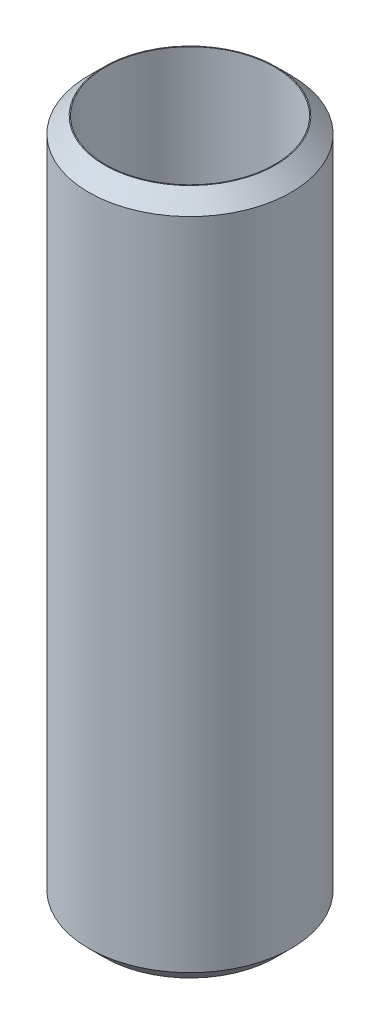
SolidWorks part; units mm, degrees
ref_plane "Front Plane" through (0, 0, 0) normal (0, 0, 1) x (1, 0, 0)
ref_plane "Top Plane" through (0, 0, 0) normal (0, 1, 0) x (1, 0, 0)
ref_plane "Right Plane" through (0, 0, 0) normal (1, 0, 0) x (0, 0, -1)
sketch "Sketch1" plane through (0, 0, 0) normal (0, 1, 0) x (1, 0, 0)
  circle A0 centre (0, 0) radius 35
  dimension "SHAFT_OD" = 70
extrude "Boss-Extrude1" add sketch "Sketch1" along normal blind 237.2817
sketch "Sketch2" plane through (0, 0, 0) normal (0, 1, 0) x (1, 0, 0)
  circle A0 centre (0, 0) radius 29.2516
  dimension "BORE_D" = 58.5033
extrude "Cut-Extrude1" cut sketch "Sketch2" along normal through all
chamfer "Chamfer1" distance 5.4442 angle 45 2 edges at (0, 237.2817, 35) (0, 0, 35)
